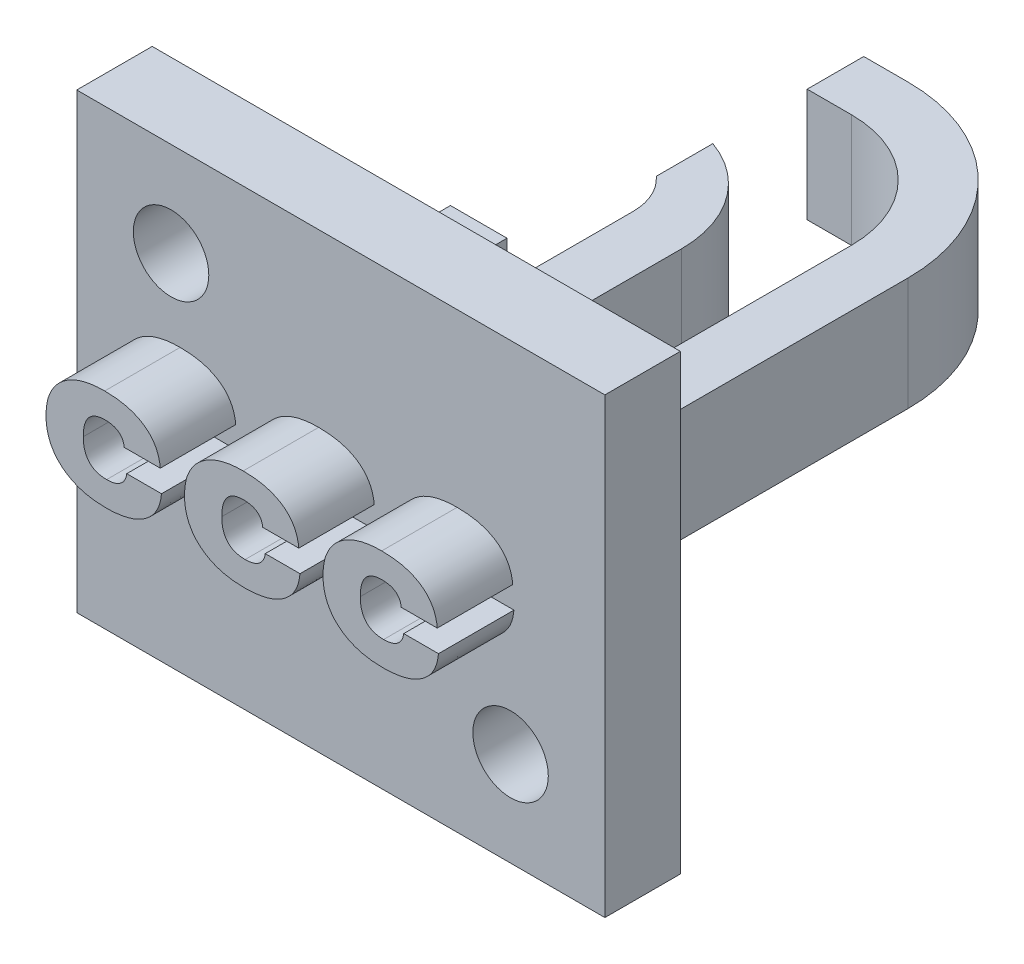
SolidWorks part; units mm, degrees
ref_plane "Front Plane" through (0, 0, 0) normal (0, 0, 1) x (1, 0, 0)
ref_plane "Top Plane" through (0, 0, 0) normal (0, 1, 0) x (1, 0, 0)
ref_plane "Right Plane" through (0, 0, 0) normal (1, 0, 0) x (0, 0, -1)
sketch "Sketch1" plane through (0, 0, 0) normal (0, 0, 1) x (1, 0, 0)
  line L1 (-7.5, 6) -> (7.5, 6)
  line L2 (-7.5, 6) -> (-7.5, -6)
  line L3 (-7.5, -6) -> (7.5, -6)
  line L4 (7.5, 6) -> (7.5, -6)
  line L5 (-7.5, 6) -> (7.5, -6) construction
  line L6 (-7.5, -6) -> (7.5, 6) construction
  point P0 (0, 0)
  dimension "D1" = 15
  dimension "D2" = 12
extrude "Boss-Extrude1" add sketch "Sketch1" along normal blind 2
sketch "Sketch2" plane through (0, 0, 2) normal (0, 0, 1) x (1, 0, 0)
  text T0 "CCC" font "Swis721 Blk BT" height in points 10
  dimension "D1" = 6.48
  dimension "D2" = 1.1738
extrude "Boss-Extrude2" add sketch "Sketch2" along normal blind 2
sketch "Sketch3" plane through (0, 0, 0) normal (0, 1, 0) x (1, 0, 0)
  line L0 (7.5, 0) -> (-7.5, 0) construction
  line L1 (1.8337, 0) -> (3.3337, 0)
  line L2 (1.8337, 0) -> (1.8337, 12.2)
  line L3 (-3.644, -2) -> (-3.644, 5.3789) construction
  line L4 (3.3337, 0) -> (3.3337, 13.7)
  line L5 (-4.394, 0) -> (-2.894, 0)
  line L6 (-4.394, 0) -> (-4.394, 4.8)
  line L7 (-1.0877, -2) -> (-1.0877, 4.6797) construction
  line L8 (-2.894, 0) -> (-2.894, 4.8)
  line L9 (-2.894, 4.8) -> (-4.394, 4.8)
  line L10 (-1.8377, 0) -> (-0.3377, 0)
  line L11 (7.5, -2) -> (-7.5, -2) construction
  line L12 (2.5837, -4) -> (2.5837, -2) construction
  line L13 (-1.8377, 0) -> (-1.8377, 8.2)
  line L14 (2.5837, -2) -> (2.5837, 2.787) construction
  line L15 (-0.3377, 0) -> (-0.3377, 9.7)
  line L16 (-0.3377, 9.7) -> (-2.3377, 9.7)
  line L17 (-2.3377, 13.7) -> (3.3337, 13.7)
  line L18 (-1.8377, 8.2) -> (-2.3377, 8.2)
  line L19 (-2.3377, 9.7) -> (-2.3377, 8.2)
  line L20 (-2.3377, 13.7) -> (-2.3377, 12.2)
  line L21 (-2.3377, 12.2) -> (1.8337, 12.2)
  line L22 (-1.0877, -4) -> (-1.0877, -2) construction
  dimension "D1" = 1.5
  dimension "D2" = 4.8
  dimension "D3" = 1.5
  dimension "D4" = 1.5
  dimension "D5" = 8.2
  dimension "D6" = 1.5
  dimension "D7" = 2.5
  dimension "D8" = 1.5
  dimension "D9" = 0.5
extrude "Boss-Extrude3" add sketch "Sketch3" along normal mid plane 3
fillet "Fillet3" radius 1.5 1 edges at (-1.8377, 0, -8.2)
fillet "Fillet4" radius 3 1 edges at (-0.3377, 0, -9.7)
fillet "Fillet5" radius 3 1 edges at (1.8337, 0, -12.2)
fillet "Fillet6" radius 4.5 1 edges at (3.3337, 0, -13.7)
sketch "Sketch4" plane through (7.5, 0, 0) normal (1, 0, 0) x (0, 0, -1)
  line L4 (0, -6) -> (0, 6)
  line L5 (0, 6) -> (-2, 6)
  line L6 (-2, 6) -> (-2, -6)
  line L7 (-2, -6) -> (0, -6)
  line L8 (0, -6) -> (0, 6)
  line L9 (0, 6) -> (-2, 6)
  line L10 (-2, 6) -> (-2, -6)
  line L11 (-2, -6) -> (0, -6)
  dimension "D1" = 0
extrude "Cut-Extrude1" cut sketch "Sketch4" against normal blind 1
sketch "Sketch5" plane through (0, 0, 0) normal (0, 0, -1) x (-1, 0, 0)
  line L0 (-6.5, -6) -> (-6.5, 6) construction
  line L1 (7.5, -6) -> (-6.5, -6) construction
  line L2 (7.5, 6) -> (7.5, -6) construction
  line L3 (-6.5, 6) -> (7.5, 6) construction
  circle A0 centre (-4, -3.5) radius 1
  circle A1 centre (5, 3.5) radius 1
  dimension "D1" = 2
  dimension "D2" = 2.5
  dimension "D3" = 2.5
  dimension "D4" = 2.5
  dimension "D5" = 2.5
extrude "Cut-Extrude2" cut sketch "Sketch5" against normal through all
